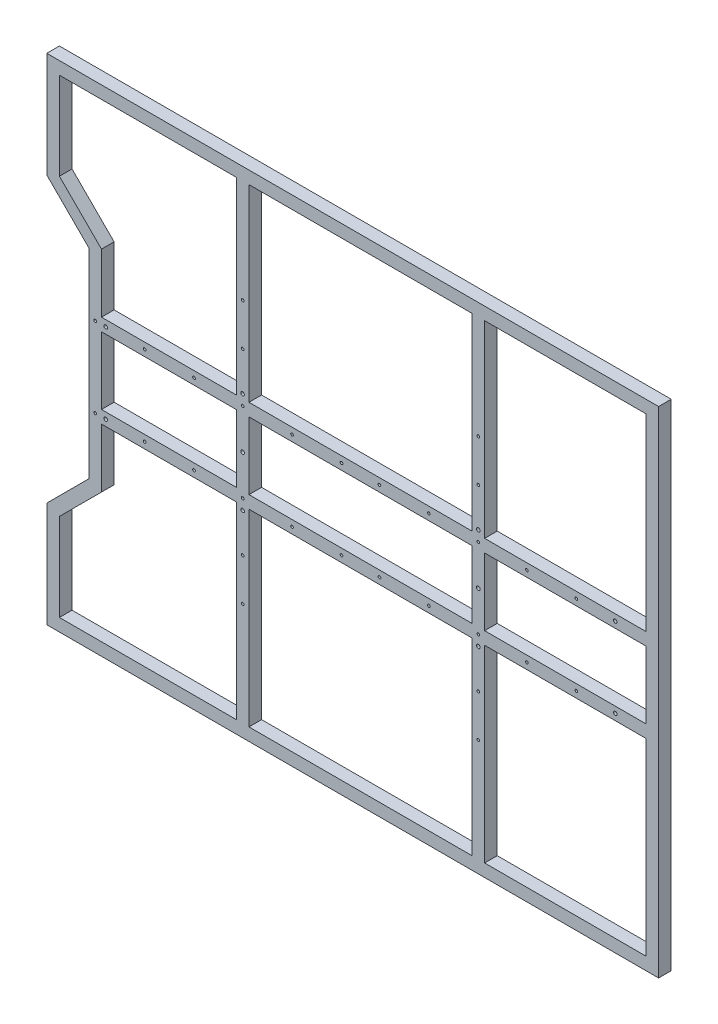
SolidWorks part; units mm, degrees
material "6061 合金"
ref_plane "前视基准面" through (0, 0, 0) normal (0, 0, 1) x (1, 0, 0)
ref_plane "上视基准面" through (0, 0, 0) normal (0, 1, 0) x (1, 0, 0)
ref_plane "右视基准面" through (0, 0, 0) normal (1, 0, 0) x (0, 0, -1)
sketch "草图2" plane through (0, 0, 0) normal (0, 0, 1) x (1, 0, 0)
  line L0 (0, 0) -> (56.6289, 0) construction
  line L1 (-372.7002, 294) -> (354.2002, 294)
  line L2 (-372.7002, 294) -> (-372.7002, 295.2267)
  line L3 (-357.7002, 279) -> (-147.5, 279)
  line L4 (354.2002, 294) -> (354.2002, 295)
  line L5 (-372.7002, 294) -> (-362.7002, 294)
  line L6 (-372.7002, 294) -> (-372.7002, 168.7868)
  line L8 (-357.7002, 279) -> (-357.7002, 175)
  line L10 (-372.7002, 168.7868) -> (-372.7002, 184.8427)
  line L17 (-307.7002, 40) -> (-147.5, 40)
  line L18 (-322.7002, 40.0093) -> (-322.7002, 55)
  line L19 (-307.7002, 55) -> (-147.5, 55)
  line L20 (354.2002, 40) -> (354.2002, 55)
  line L22 (354.2002, 40) -> (354.2002, 294)
  line L23 (354.2002, 294) -> (346.2002, 294)
  line L24 (339.2002, 55) -> (339.2002, 279)
  line L26 (147.5, 55) -> (147.5, 279)
  line L27 (147.5, 294) -> (132.5, 294)
  line L28 (132.5, 55) -> (132.5, 279)
  line L30 (-132.5, 55) -> (-132.5, 279)
  line L31 (-132.5, 294) -> (-147.5, 294)
  line L32 (-147.5, 55) -> (-147.5, 279)
  line L33 (291.2002, 87.2824) -> (291.2002, 180.1039) construction
  line L34 (-357.7002, 175) -> (-307.7002, 125)
  line L35 (-307.7002, 125) -> (-307.7002, 105)
  line L36 (-322.7002, 118.7868) -> (-372.7002, 168.7868)
  line L37 (-132.5, 55) -> (132.5, 55)
  line L38 (-322.7002, 118.7868) -> (-322.7002, 40.0093)
  line L39 (-307.7002, 125) -> (-307.7002, 55)
  line L40 (-132.5, 279) -> (132.5, 279)
  line L41 (147.5, 279) -> (339.2002, 279)
  line L42 (147.5, 55) -> (339.2002, 55)
  line L43 (147.5, -55) -> (339.2002, -55)
  line L44 (147.5, -279) -> (339.2002, -279)
  line L45 (-132.5, -279) -> (132.5, -279)
  line L46 (-307.7002, -125) -> (-307.7002, -55)
  line L47 (-322.7002, -118.7868) -> (-322.7002, -40.0093)
  line L48 (-132.5, -55) -> (132.5, -55)
  line L49 (-322.7002, -118.7868) -> (-372.7002, -168.7868)
  line L50 (-307.7002, -125) -> (-307.7002, -105)
  line L51 (-357.7002, -175) -> (-307.7002, -125)
  line L52 (-147.5, -55) -> (-147.5, -279)
  line L53 (-132.5, -294) -> (-147.5, -294)
  line L54 (-132.5, -55) -> (-132.5, -279)
  line L56 (132.5, -55) -> (132.5, -279)
  line L57 (147.5, -294) -> (132.5, -294)
  line L58 (147.5, -55) -> (147.5, -279)
  line L59 (-132.5, -40) -> (132.5, -40)
  line L60 (339.2002, -55) -> (339.2002, -279)
  line L61 (354.2002, -294) -> (346.2002, -294)
  line L62 (354.2002, -40) -> (354.2002, -294)
  line L63 (147.5, 40) -> (339.2002, 40)
  line L64 (354.2002, -40) -> (354.2002, -55)
  line L65 (-307.7002, -55) -> (-147.5, -55)
  line L66 (-322.7002, -40.0093) -> (-322.7002, -55)
  line L67 (-307.7002, -40) -> (-147.5, -40)
  line L68 (-372.7002, -168.7868) -> (-372.7002, -184.8427)
  line L69 (-366.6895, -163.0534) -> (-363.8898, -163.0534)
  line L70 (-357.7002, -279) -> (-357.7002, -175)
  line L71 (-366.6895, -163.0534) -> (-363.8898, -163.0534)
  line L72 (-372.7002, -294) -> (-372.7002, -168.7868)
  line L73 (-372.7002, -294) -> (-362.7002, -294)
  line L74 (354.2002, -294) -> (354.2002, -295)
  line L75 (-357.7002, -279) -> (-147.5, -279)
  line L76 (-372.7002, -294) -> (-372.7002, -295.2267)
  line L77 (-372.7002, -294) -> (354.2002, -294)
  line L78 (147.5, -40) -> (339.2002, -40)
  line L80 (-322.7002, 40.0093) -> (-322.7002, -40.0093)
  line L82 (-307.7002, 40) -> (-307.7002, -40)
  line L84 (-147.5, 40) -> (-147.5, -40)
  line L86 (-132.5, 40) -> (-132.5, -40)
  line L88 (132.5, 40) -> (132.5, -40)
  line L90 (147.5, 40) -> (147.5, -40)
  line L92 (339.2002, 40) -> (339.2002, -40)
  line L94 (354.2002, 40) -> (354.2002, -40)
  line L95 (-132.5, 40) -> (132.5, 40)
  circle A0 centre (140, 60) radius 2.1 construction
  circle A1 centre (-140, 60) radius 2.1 construction
  circle A2 centre (-302.7002, 47.5) radius 2.15 construction
  circle A3 centre (-327.7002, 47.5) radius 2.15 construction
  dimension "D8" = 7.5
  dimension "D9" = 7.5
  dimension "D11" = 7.5
  dimension "D12" = 15
  dimension "D15" = 5
  dimension "D1" = 15
  dimension "D2" = 15
  dimension "D3" = 15
  dimension "D4" = 15
  dimension "D5" = 50
  dimension "D6" = 15
  dimension "D7" = 15
  dimension "D10" = 224
  dimension "D13" = 15
  dimension "D14" = 48
  dimension "D16" = 15
  dimension "D17" = 50
  dimension "D18" = 70
  dimension "D19" = 135
extrude "凸台-拉伸1" add sketch "草图2" along normal blind 15 contours L94 L20 L22 L4 L1 L2 L6 L36 L38 L18 L80 L47 L49 L68 L72 L73 L77 L53 L57 L61 L62 L75 L70 L51 L46 L65 L52 L42 L26 region at (-367.7002, 284.6505, 0)
sketch "草图3" plane through (0, 0, 15) normal (0, 0, 1) x (1, 0, 0)
  line L0 (-170, 60) -> (-110, 60) construction
  line L1 (40.1698, 0) -> (-40.1698, 0) construction
  line L2 (0, 0) -> (0, 60) construction
  line L3 (-140, 153.0178) -> (-140, -19.3646) construction
  line L4 (-315.2002, 47.5) -> (315.2002, 47.5) construction
  line L5 (-307.7002, 55) -> (-147.5, 55) construction
  line L6 (-322.7002, 118.7868) -> (-322.7002, -118.7868) construction
  line L7 (140, 153.0178) -> (140, -19.3646) construction
  line L8 (170, 60) -> (110, 60) construction
  circle A0 centre (-140, 60) radius 2.15
  circle A1 centre (-315.2002, 47.5) radius 1.6
  circle A2 centre (-256.4668, 47.5) radius 1.6
  circle A3 centre (-197.7368, 47.5) radius 1.6
  circle A4 centre (-140, 47.5) radius 1.6
  circle A6 centre (-140, 156.23) radius 1.6
  circle A7 centre (-140, 106.23) radius 1.6
  circle A8 centre (-81.27, 47.5) radius 1.6
  circle A9 centre (-22.54, 47.5) radius 1.6
  circle A10 centre (-140, 0) radius 2.2407
  circle A11 centre (-302.7002, 47.5) radius 2.15 construction
  circle A12 centre (-302.7002, 47.5) radius 2.15
  circle A13 centre (-302.7002, -47.5) radius 2.15
  circle A14 centre (-22.54, -47.5) radius 1.6
  circle A15 centre (-81.27, -47.5) radius 1.6
  circle A16 centre (-140, -106.23) radius 1.6
  circle A17 centre (-140, -156.23) radius 1.6
  circle A18 centre (-140, -47.5) radius 1.6
  circle A19 centre (-197.7368, -47.5) radius 1.6
  circle A20 centre (-256.4668, -47.5) radius 1.6
  circle A21 centre (-315.2002, -47.5) radius 1.6
  circle A22 centre (-140, -60) radius 2.15
  circle A23 centre (140, -60) radius 2.15
  circle A25 centre (256.4668, -47.5) radius 1.6
  circle A26 centre (197.7368, -47.5) radius 1.6
  circle A27 centre (140, -47.5) radius 1.6
  circle A28 centre (140, -156.23) radius 1.6
  circle A29 centre (140, -106.23) radius 1.6
  circle A30 centre (81.27, -47.5) radius 1.6
  circle A31 centre (22.54, -47.5) radius 1.6
  circle A32 centre (302.7002, -47.5) radius 2.15
  circle A33 centre (302.7002, 47.5) radius 2.15
  circle A34 centre (140, 0) radius 2.2407
  circle A35 centre (22.54, 47.5) radius 1.6
  circle A36 centre (81.27, 47.5) radius 1.6
  circle A37 centre (140, 106.23) radius 1.6
  circle A38 centre (140, 156.23) radius 1.6
  circle A39 centre (140, 47.5) radius 1.6
  circle A40 centre (197.7368, 47.5) radius 1.6
  circle A41 centre (256.4668, 47.5) radius 1.6
  circle A43 centre (140, 60) radius 2.15
  point P63 (0, 47.5)
  dimension "D1" = 4.3
  dimension "D10" = 3.2
  dimension "D2" = 7.5
  dimension "D3" = 7.5
  dimension "D4" = 58.7333
  dimension "D5" = 58.73
  dimension "D6" = 58.73
  dimension "D7" = 50
  dimension "D8" = 58.73
  dimension "D9" = 58.73
extrude "切除-拉伸1" cut sketch "草图3" against normal blind 15
